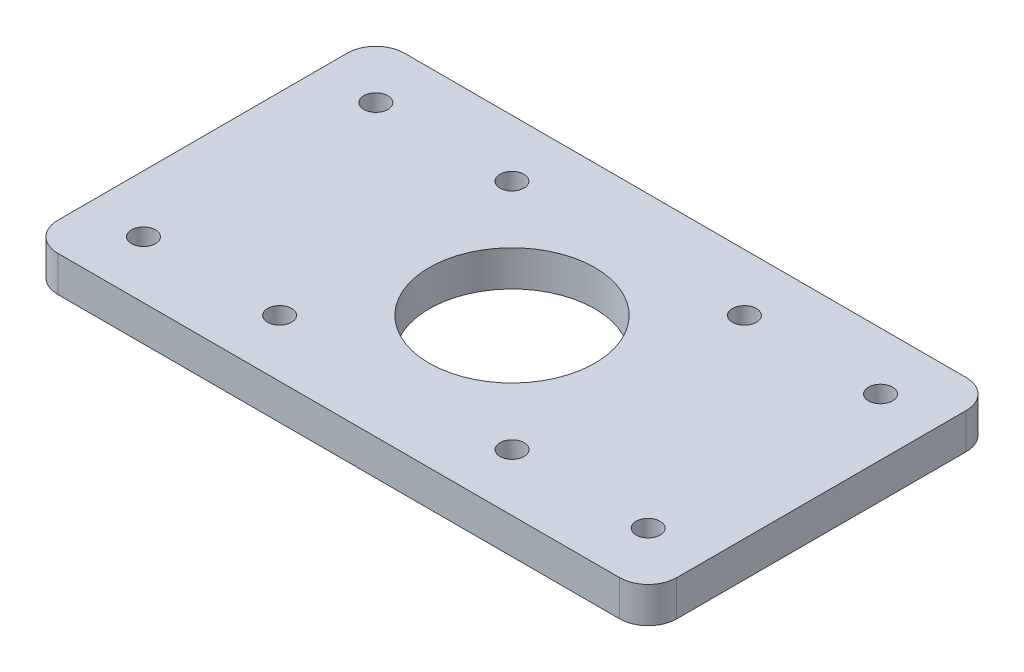
SolidWorks part; units mm, degrees
ref_plane "Front" through (0, 0, 0) normal (0, 0, 1) x (1, 0, 0)
ref_plane "Top" through (0, 0, 0) normal (0, 1, 0) x (1, 0, 0)
ref_plane "Right" through (0, 0, 0) normal (1, 0, 0) x (0, 0, -1)
sketch "Sketch1" plane through (0, 0, 0) normal (0, 1, 0) x (1, 0, 0)
  line L0 (41.275, 46.228) -> (41.275, 0) construction
  line L1 (0, 0) -> (82.55, 0)
  line L2 (0, 0) -> (0, 46.228)
  line L3 (0, 46.228) -> (82.55, 46.228)
  line L4 (82.55, 0) -> (82.55, 46.228)
  line L5 (0, 23.114) -> (82.55, 23.114) construction
  circle A0 centre (74.93, 38.608) radius 1.6
  circle A1 centre (7.62, 38.608) radius 1.6
  circle A2 centre (74.93, 7.62) radius 1.6
  circle A3 centre (7.62, 7.62) radius 1.6
  circle A4 centre (41.275, 23.114) radius 11.049
  circle A5 centre (25.775, 38.608) radius 1.6
  circle A6 centre (56.775, 38.608) radius 1.6
  circle A7 centre (25.775, 7.62) radius 1.6
  circle A8 centre (56.775, 7.62) radius 1.6
  dimension "D3" = 3.2
  dimension "D6" = 22.098
  dimension "D7" = 31
  dimension "D8" = 30.988
  dimension "D1" = 82.55
  dimension "D2" = 46.228
  dimension "D4" = 7.62
  dimension "D5" = 7.62
extrude "Boss-Extrude1" add sketch "Sketch1" along normal blind 4.7625
fillet "Fillet1" radius 3.81 4 edges at (82.55, 2.3813, -46.228) (82.55, 2.3813, 0) (0, 2.3813, 0) (0, 2.3813, -46.228)
